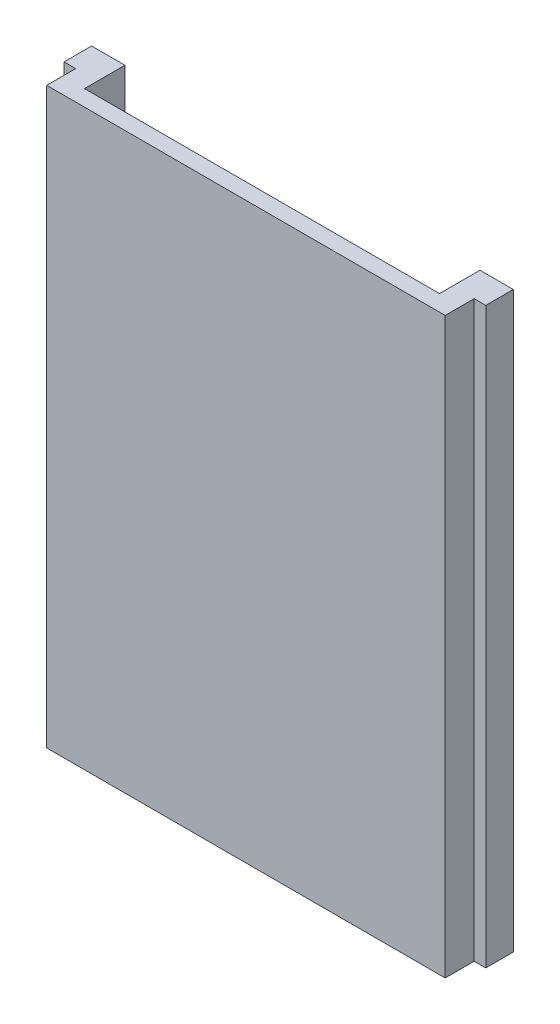
SolidWorks part; units mm, degrees
ref_plane "Alzado" through (0, 0, 0) normal (0, 0, 1) x (1, 0, 0)
ref_plane "Planta" through (0, 0, 0) normal (0, 1, 0) x (1, 0, 0)
ref_plane "Vista lateral" through (0, 0, 0) normal (1, 0, 0) x (0, 0, -1)
sketch "Croquis1" plane through (0, 0, 0) normal (0, 1, 0) x (1, 0, 0)
  line L5 (-4, 10) -> (-4, 19.5)
  line L14 (7.5, 19.5) -> (7.5, 5.5361)
  line L17 (-4, 19.5) -> (7.5, 19.5)
  line L19 (0, 0) -> (137.5, 0)
  line L20 (0, 0) -> (0, 10)
  line L21 (0, 10) -> (-4, 10)
  line L23 (7.5, 5.5361) -> (130, 5.5361)
  line L25 (68.75, 54.2093) -> (68.75, -41.2998) construction
  line L26 (137.5, 10) -> (141.5, 10)
  line L27 (137.5, 0) -> (137.5, 10)
  line L28 (141.5, 19.5) -> (130, 19.5)
  line L29 (130, 19.5) -> (130, 5.5361)
  line L30 (141.5, 10) -> (141.5, 19.5)
  point P3 (68.75, 5.5361)
  point P12 (68.75, 0)
  dimension "D1" = 68.75
  dimension "D2" = 10
  dimension "D3" = 9.5
  dimension "D4" = 11.5
  dimension "D5" = 72.75
  dimension "D7" = 5.5361
extrude "Saliente-Extruir4" add sketch "Croquis1" along normal blind 198 contours L17 L14 L23 L29 L28 L30 L26 L27 L19 L20 L21 L5
ref_plane "Plano1" through (68.75, 0, 0) normal (1, 0, 0) x (0, 0, -1)
sketch "Croquis2" plane through (0, 0, -5.5361) normal (0, 0, -1) x (-1, 0, 0)
  line L0 (-7.5, 0) -> (-130, 0) construction
  line L1 (-7.5, 0) -> (-130, 0) construction
  line L2 (-7.5, 198) -> (-7.5, 0) construction
  line L3 (-130, 198) -> (-130, 0) construction
  line L4 (-7.5, 198) -> (-7.5, 0) construction
  line L5 (-130, 198) -> (-130, 0) construction
  line L6 (-130, 108) -> (-7.5, 108)
  line L7 (-130, 105) -> (-7.5, 105)
  line L8 (-130, 108) -> (-130, 105)
  line L9 (-7.5, 108) -> (-7.5, 105)
  dimension "D1" = 108
  dimension "D2" = 3
extrude "Saliente-Extruir5" add sketch "Croquis2" along normal up to surface (13.9639 mm away) up to face at (135.75, 99, -19.5)
